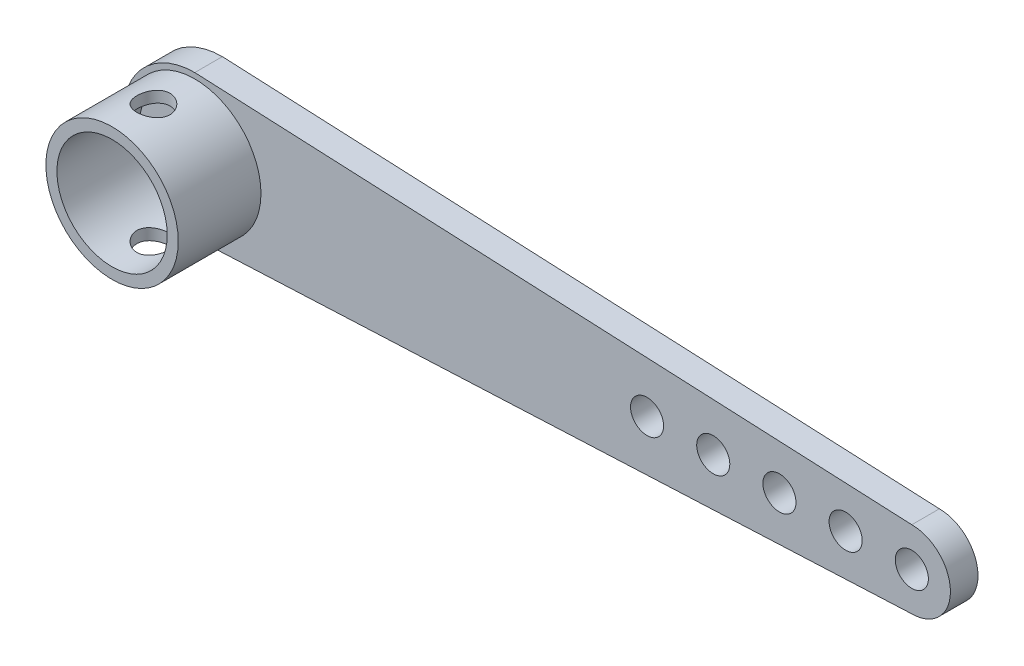
SolidWorks part; units mm, degrees
ref_plane "Płaszczyzna przednia" through (0, 0, 0) normal (0, 0, 1) x (1, 0, 0)
ref_plane "Płaszczyzna górna" through (0, 0, 0) normal (0, 1, 0) x (1, 0, 0)
ref_plane "Płaszczyzna prawa" through (0, 0, 0) normal (1, 0, 0) x (0, 0, -1)
sketch "Szkic2" plane through (0, 0, 0) normal (0, 0, 1) x (1, 0, 0)
  line L0 (0, 13) -> (130, 7)
  line L1 (0, -13) -> (130, -7)
  circle A0 centre (0, 0) radius 13
  circle A1 centre (130, 0) radius 7
  dimension "D1" = 26
  dimension "D2" = 14
  dimension "D3" = 130
extrude "Dodanie-wyciągnięcie1" add sketch "Szkic2" along normal blind 5 contours A1 L0 A0 L1 | A1 | L0 A0 L1 region at (0, 0, 0) region at (62.3931, 0, 0) region at (130, 0, 0)
sketch "Szkic5" plane through (0, 0, 5) normal (0, 0, 1) x (1, 0, 0)
  circle A0 centre (0, 0) radius 12
  dimension "D1" = 24
extrude "Dodanie-wyciągnięcie3" add sketch "Szkic5" along normal blind 15
sketch "Szkic6" plane through (0, 0, 20) normal (0, 0, 1) x (1, 0, 0)
  circle A0 centre (0, 0) radius 10
  dimension "D1" = 20
extrude "Wytnij-wyciągnięcie1" cut sketch "Szkic6" against normal blind 15
sketch "Szkic7" plane through (0, 0, 0) normal (0, 1, 0) x (1, 0, 0)
  circle A0 centre (0, -12.5) radius 3
  dimension "D1" = 6
  dimension "D2" = 7.5
extrude "Wytnij-wyciągnięcie2" cut sketch "Szkic7" against normal mid plane 43
sketch "Szkic8" plane through (0, 0, 5) normal (0, 0, 1) x (1, 0, 0)
  circle A0 centre (130, 0) radius 3
  circle A1 centre (118, 0) radius 3
  circle A2 centre (106, 0) radius 3
  circle A3 centre (94, 0) radius 3
  circle A4 centre (82, 0) radius 3
  dimension "D1" = 6
  dimension "D2" = 6
  dimension "D3" = 6
  dimension "D4" = 6
  dimension "D5" = 6
  dimension "D6" = 12
  dimension "D7" = 12
  dimension "D8" = 12
  dimension "D9" = 12
extrude "Wytnij-wyciągnięcie3" cut sketch "Szkic8" against normal blind 43
